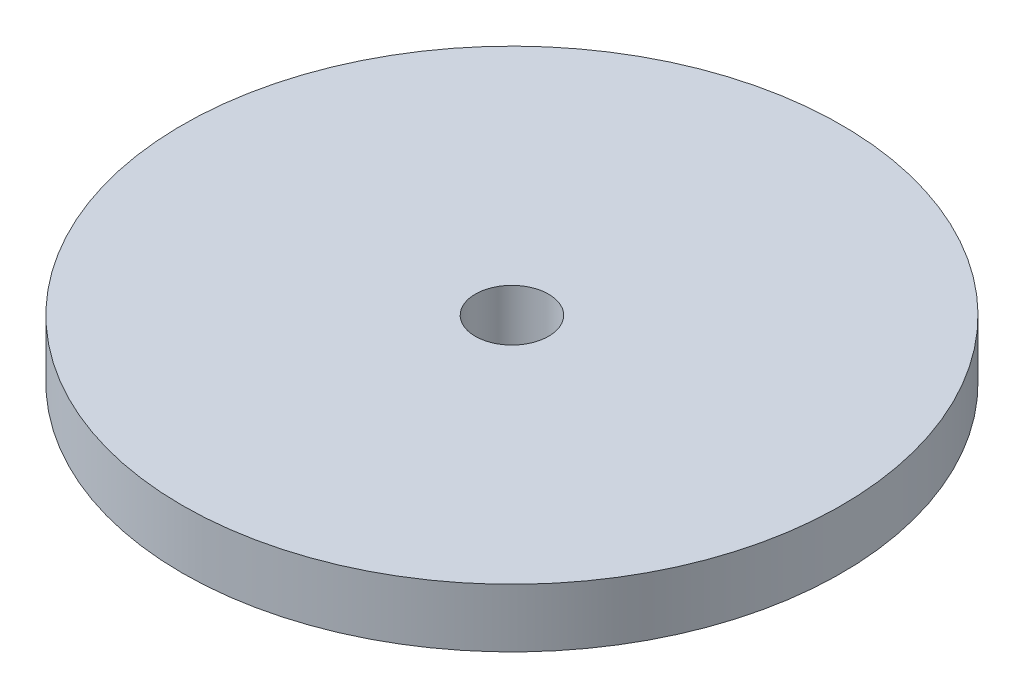
SolidWorks part; units mm, degrees
ref_plane "Plan de face" through (0, 0, 0) normal (0, 0, 1) x (1, 0, 0)
ref_plane "Plan de dessus" through (0, 0, 0) normal (0, 1, 0) x (1, 0, 0)
ref_plane "Plan de droite" through (0, 0, 0) normal (1, 0, 0) x (0, 0, -1)
sketch "Esquisse1" plane through (0, 0, 0) normal (0, 0, 1) x (1, 0, 0)
  line L0 (0, 8.6266) -> (0, -8.6266) construction
  line L1 (2.5, 2) -> (2.5, -13)
  line L2 (2.5, -13) -> (4, -13)
  line L3 (4, -13) -> (4, -2)
  line L6 (4, -2) -> (22.5, -2)
  line L7 (22.5, -2) -> (22.5, 2)
  line L12 (22.5, 2) -> (2.5, 2)
  line L13 (0, 0) -> (37.2784, 0) construction
  dimension "D1" = 4
  dimension "D2" = 45
  dimension "D3" = 5
  dimension "D4" = 8
  dimension "D5" = 15
revolve "Révolution1" add sketch "Esquisse1" angle 360 about L0
